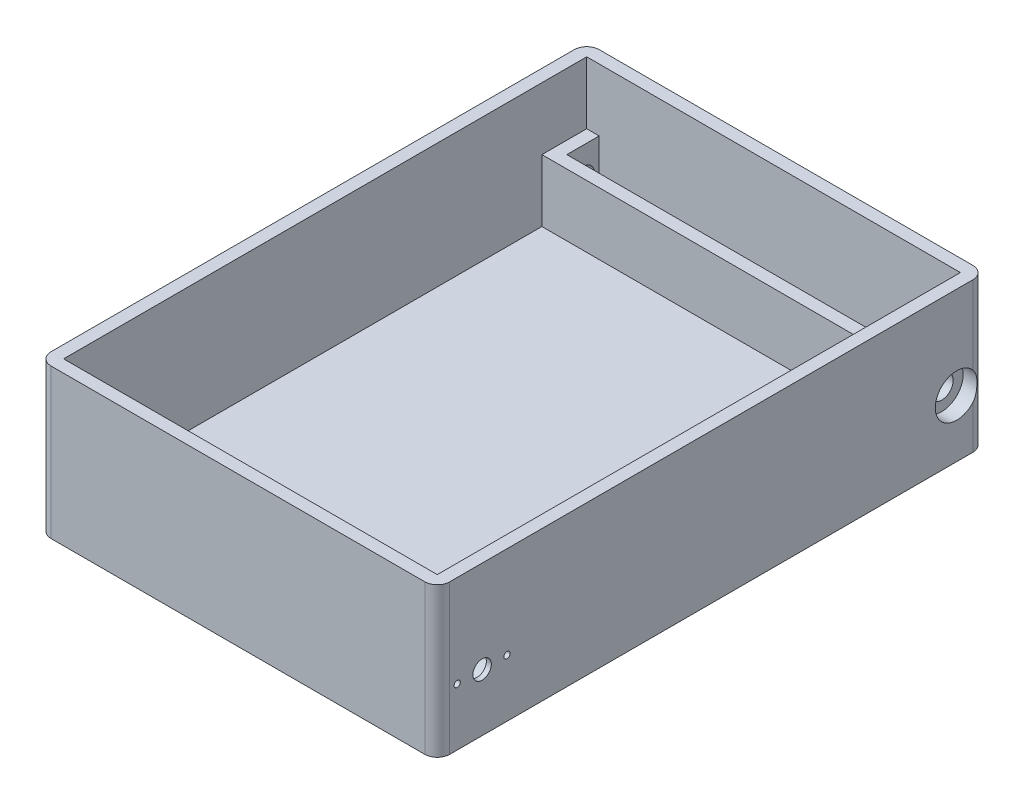
SolidWorks part; units mm, degrees
ref_plane "Front Plane" through (0, 0, 0) normal (0, 0, 1) x (1, 0, 0)
ref_plane "Top Plane" through (0, 0, 0) normal (0, 1, 0) x (1, 0, 0)
ref_plane "Right Plane" through (0, 0, 0) normal (1, 0, 0) x (0, 0, -1)
sketch "Main Body" plane through (0, 0, 0) normal (0, 1, 0) x (1, 0, 0)
  line L0 (-75, 110) -> (75, 110)
  line L1 (-75, -105) -> (75, -105)
  line L2 (-75, -105) -> (-75, 105)
  line L3 (-75, 105) -> (75, 105)
  line L4 (75, -105) -> (75, 105)
  line L5 (-75, -105) -> (75, 105) construction
  line L6 (-75, 105) -> (75, -105) construction
  line L7 (80, -105) -> (80, 105)
  line L8 (-75, -110) -> (75, -110)
  line L9 (-80, -105) -> (-80, 105)
  line L10 (-80, -110) -> (80, -110) construction
  line L11 (-80, -110) -> (-80, 110) construction
  line L12 (80, -110) -> (80, 110) construction
  line L13 (-80, 110) -> (80, 110) construction
  arc A0 (-75, -110) -> (-80, -105) centre (-75, -105) cw
  arc A1 (80, -105) -> (75, -110) centre (75, -105) cw
  arc A2 (75, 110) -> (80, 105) centre (75, 105) cw
  arc A3 (-75, 110) -> (-80, 105) centre (-75, 105) ccw
  point P0 (0, 0)
  dimension "D4" = 5
  dimension "D1" = 75
  dimension "D2" = 210
  dimension "D3" = 5
extrude "Boss-Extrude1" add sketch "Main Body" along normal blind 10 contours L1 L4 L3 L2 | L9 L8 L7 L0 L4 L1 L2 L3 region at (0, 0, -107.2797) region at (0, 0, 0)
extrude "Boss-Extrude3" add sketch "Main Body<4>" along normal blind 50 from surface starting at face at (0, 10, 0)
sketch "Main Body<4>" plane through (0, 0, 0) normal (0, 1, 0) x (1, 0, 0) same geometry as "Main Body"
sketch "Sketch1" plane through (75, 0, 0) normal (-1, 0, 0) x (0, 0, 1)
  line L0 (105, 60) -> (105, 10) construction
  line L1 (-105, 10) -> (105, 10) construction
  line L2 (79, 17.5) -> (105, 17.5)
  line L3 (79, 10) -> (105, 10)
  line L4 (79, 10) -> (79, 36)
  line L5 (79, 36) -> (105, 36)
  line L6 (105, 10) -> (105, 36)
  line L7 (79, 10) -> (105, 36) construction
  line L8 (79, 36) -> (105, 10) construction
  circle A0 centre (92, 23) radius 13
  line M2 (-105, 10) -> (105, 10)
  line M3 (105, 10) -> (105, 60)
  dimension "D1" = 26
  dimension "D2" = 7.5
extrude "Boss-Extrude4" add sketch "Sketch1" along normal up to surface (150 mm away) contours A0 L4 M2 | A0 L3 M3 region at (75, 12.5201, 82.0674) region at (75, 12.5201, 101.9326) up to face at (-75, 35, 0)
sketch "Sketch2" plane through (0, 0, 0) normal (1, 0, 0) x (0, 0, -1)
  line L0 (-105, 60) -> (-105, 17.5) construction
  line L1 (-105, 10) -> (-79, 10)
  line L2 (-105, 10) -> (-105, 17.5)
  line L3 (-105, 17.5) -> (-79, 17.5)
  line L4 (-79, 10) -> (-79, 17.5)
  line L5 (105, 10) -> (-79, 10) construction
  line L6 (-79, 10) -> (-79, 17.5) construction
  line L7 (-79, 17.5) -> (-80.2208, 17.5) construction
extrude "Cut-Extrude1" cut sketch "Sketch2" against normal mid plane 12
sketch "Sketch3" plane through (0, 10, 0) normal (0, 1, 0) x (1, 0, 0)
  line L0 (75, -105) -> (-75, -105) construction
  line L1 (-6, -79) -> (-11, -79)
  line L2 (-6, -79) -> (-6, -105)
  line L3 (-6, -105) -> (-11, -105)
  line L4 (-11, -79) -> (-11, -105)
  line L5 (0, 0) -> (0, -105) construction
  line L6 (-75, -79) -> (-6, -79) construction
  line L7 (11, -79) -> (11, -105)
  line L8 (6, -105) -> (11, -105)
  line L9 (6, -79) -> (6, -105)
  line L10 (6, -79) -> (11, -79)
  dimension "D1" = 5
extrude "Boss-Extrude5" add sketch "Sketch3" along normal up to surface (7.5 mm away) up to face at (40.5, 17.5, 79.6104)
sketch "Sketch4" plane through (0, 10, 0) normal (0, 1, 0) x (1, 0, 0)
  line L0 (-75, -105) -> (-75, 105) construction
  line L1 (-75, 92) -> (75, 92)
  line L2 (-75, 92) -> (-75, 87)
  line L3 (-75, 87) -> (75, 87)
  line L4 (75, 92) -> (75, 87)
  line L5 (75, 105) -> (75, -105) construction
  line L6 (-75, 105) -> (75, 105) construction
  dimension "D1" = 18
  dimension "D2" = 5
extrude "Boss-Extrude6" add sketch "Sketch4" along normal blind 25
sketch "Sketch5" plane through (80, 0, 0) normal (1, 0, 0) x (0, 0, -1)
  circle A0 centre (-92, 23) radius 3.5 construction
  circle A1 centre (-92, 23) radius 3.5
  circle A2 centre (-92, 23) radius 3.7
  dimension "D1" = 0.2
extrude "Cut-Extrude4" cut sketch "Sketch5" against normal up to next contours A1 | A2 A1 region at (80, 23, 92) region at (80, 23, 95.5953)
sketch "Sketch6" plane through (-75, 0, 0) normal (1, 0, 0) x (0, 0, -1)
  circle A0 centre (-92, 23) radius 13
  dimension "D1" = 26
extrude "Cut-Extrude5" cut sketch "Sketch6" against normal offset from surface (3 mm away) 2 up to face at (-80, 30, 0)
mirror "Mirror1" about plane through (0, 0, 0) normal (1, 0, 0) of "Cut-Extrude4"
sketch "Sketch8" plane through (75, 0, 0) normal (-1, 0, 0) x (0, 0, 1)
  circle A0 centre (92, 23) radius 13
  dimension "D1" = 26
extrude "Cut-Extrude6" cut sketch "Sketch8" against normal offset from surface (3 mm away) 2 up to face at (80, 23, 88.3)
sketch "Sketch10" plane through (80, 0, 0) normal (1, 0, 0) x (0, 0, -1)
  circle A1 centre (-82, 23) radius 1.25
  circle A2 centre (-82, 23) radius 1.25
  circle A3 centre (-102, 23) radius 1.25
  circle A4 centre (-102, 23) radius 1.25
  circle A5 centre (-92, 23) radius 12.5
  circle A6 centre (-92, 23) radius 12.5
  dimension "D1" = 0
  dimension "D2" = 0
  dimension "D3" = 0
extrude "Cut-Extrude7" cut sketch "Sketch10" against normal up to next contours A2 | A4 region at (80, 23, 82) region at (80, 23, 102)
mirror "Mirror3" about plane through (0, 0, 0) normal (1, 0, 0) of "Cut-Extrude7"
sketch "Sketch11" plane through (80, 0, 0) normal (1, 0, 0) x (0, 0, -1)
  circle A0 centre (98.5, 23) radius 4.5 construction
  circle A1 centre (98.5, 23) radius 4.5
  circle A3 centre (98.5, 23) radius 4.6
  dimension "D1" = 0.1
extrude "Cut-Extrude10" cut sketch "Sketch11" against normal through all contours A1 | A3 A1 region at (80, 23, -98.5) region at (80, 23, -93.913)
sketch "Sketch12" plane through (-75, 0, 0) normal (1, 0, 0) x (0, 0, -1)
  line L0 (92, 10) -> (105, 10) construction
  line L1 (92, 35) -> (105, 35)
  line L2 (92, 35) -> (92, 10)
  line L3 (92, 10) -> (105, 10)
  line L4 (105, 35) -> (105, 10)
  line L6 (92, 35) -> (92, 10) construction
  line L7 (92, 35) -> (87, 35) construction
  circle A2 centre (98.5, 23) radius 4.6 construction
  circle A3 centre (98.5, 23) radius 4.6
  point P5 (93.728, 10)
extrude "Boss-Extrude7" add sketch "Sketch12" along normal blind 5
sketch "Sketch13" plane through (-80, 0, 0) normal (-1, 0, 0) x (0, 0, 1)
  circle A0 centre (-98.5, 23) radius 8.6
  circle A2 centre (-98.5, 23) radius 4.6 construction
  point P4 (0, 0)
  dimension "D1" = 17.2
extrude "Cut-Extrude11" cut sketch "Sketch13" against normal blind 6
mirror "Mirror4" about plane through (0, 0, 0) normal (1, 0, 0) of "Boss-Extrude7", "Cut-Extrude11"
